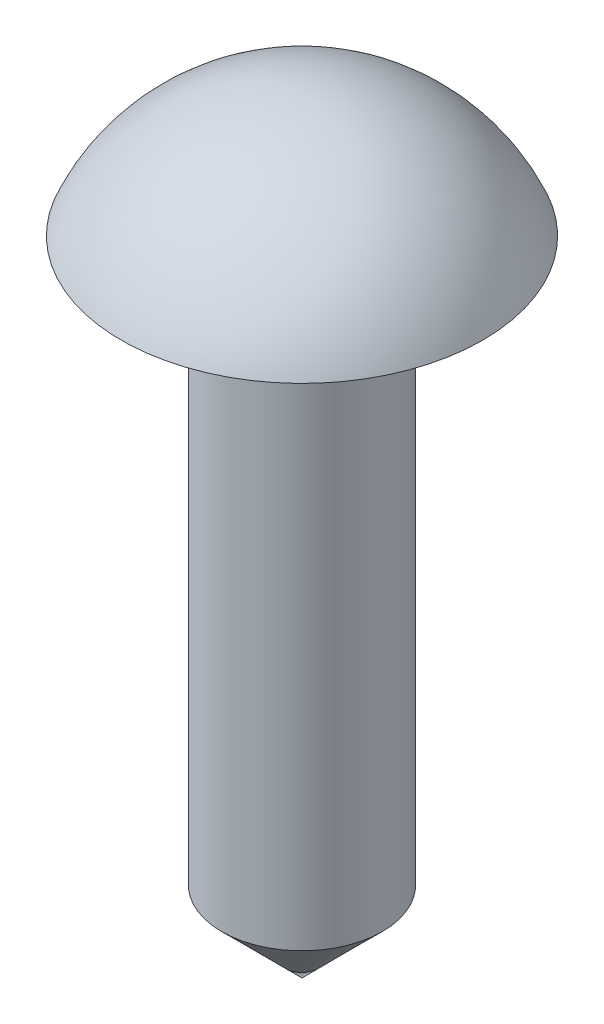
SolidWorks part; units mm, degrees
material "AISI 316 Annealed Stainless Steel Bar (SS)"
ref_plane "Front Plane" through (0, 0, 0) normal (0, 0, 1) x (1, 0, 0)
ref_plane "Top Plane" through (0, 0, 0) normal (0, 1, 0) x (1, 0, 0)
ref_plane "Right Plane" through (0, 0, 0) normal (1, 0, 0) x (0, 0, -1)
sketch "Sketch1" plane through (0, 0, 0) normal (0, 0, 1) x (1, 0, 0)
  line L0 (0, -4) -> (1, -4)
  line L1 (1, -4) -> (1, 4)
  line L2 (1, 4) -> (2.25, 4)
  line L3 (0, -593.7248) -> (0, 29092.5156) construction
  line L4 (0, 5.5) -> (0, -4)
  arc A1 (2.25, 4) -> (0, 5.5) centre (0, 3.0625) ccw
  point P5 (1, 0)
  dimension "D1" = 2
  dimension "D2" = 4.5
  dimension "D3" = 1.5
  dimension "D4" = 8
revolve "Revolve1" add sketch "Sketch1" angle 360 about L3
chamfer "Chamfer1" distance 1 angle 45 1 edges at (1, -4, 0)
